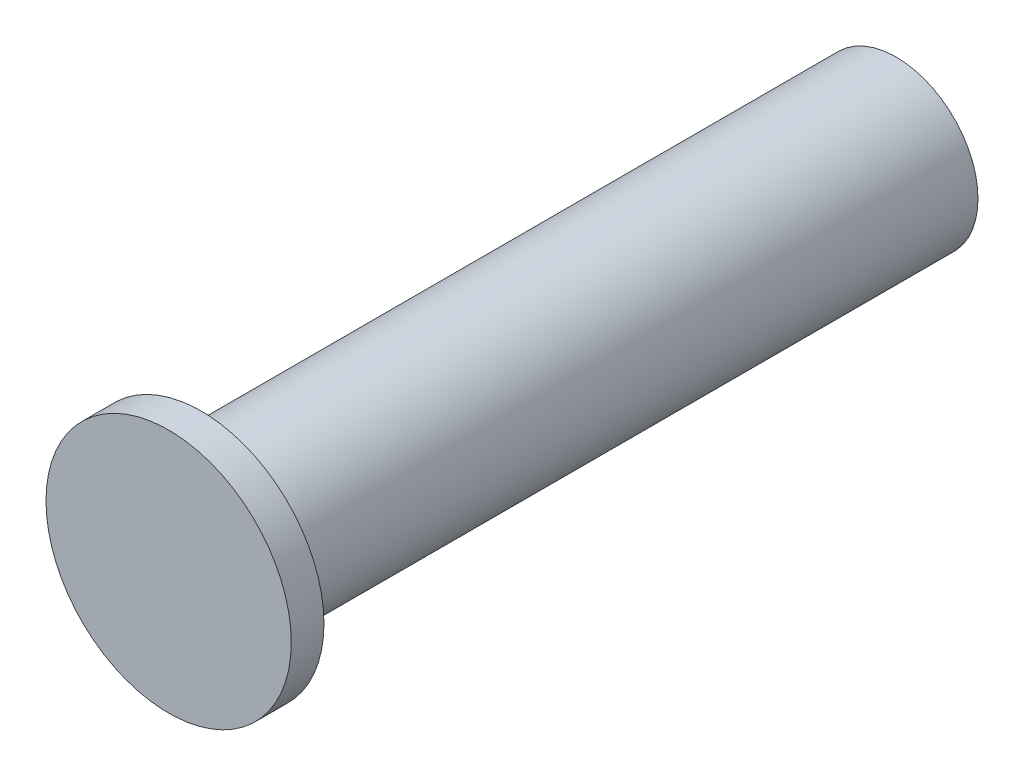
SolidWorks part; units mm, degrees
material "AISI 304"
ref_plane "Alzado" through (0, 0, 0) normal (0, 0, 1) x (1, 0, 0)
ref_plane "Planta" through (0, 0, 0) normal (0, 1, 0) x (1, 0, 0)
ref_plane "Vista lateral" through (0, 0, 0) normal (1, 0, 0) x (0, 0, -1)
ref_plane "Plano1" through (0, 0, 51.9) normal (0, 0, 1) x (1, 0, 0)
sketch "Sk_Cana" plane through (0, 0, 51.9) normal (0, 0, 1) x (1, 0, 0)
  circle A0 centre (0, 0) radius 2
extrude "Cana" add sketch "Sk_Cana" along normal blind 17
ref_plane "Plano2" through (0, 0, 68.9) normal (0, 0, 1) x (1, 0, 0)
sketch "Sk_Cabeza" plane through (0, 0, 68.9) normal (0, 0, 1) x (1, 0, 0)
  circle A0 centre (0, 0) radius 3
extrude "Cabeza" add sketch "Sk_Cabeza" along normal blind 0.8
